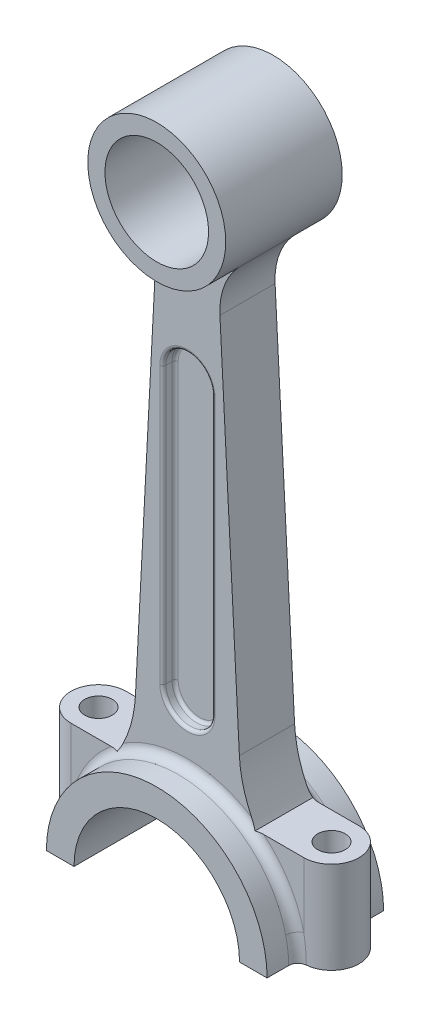
SolidWorks part; units mm, degrees
ref_plane "Front Plane" through (0, 0, 0) normal (0, 0, 1) x (1, 0, 0)
ref_plane "Top Plane" through (0, 0, 0) normal (0, 1, 0) x (1, 0, 0)
ref_plane "Right Plane" through (0, 0, 0) normal (1, 0, 0) x (0, 0, -1)
sketch "Sketch1" plane through (0, 0, 0) normal (0, 0, 1) x (1, 0, 0)
  line L0 (0, 0) -> (0, -201.2) construction
  line L1 (-10, -20.1556) -> (-17.8497, -169.9368)
  line L2 (10, -20.1556) -> (17.8497, -169.9368)
  line L3 (-36, -201.2) -> (-27, -201.2)
  line L4 (27, -201.2) -> (36, -201.2)
  circle A0 centre (0, 0) radius 16.9
  circle A1 centre (0, 0) radius 22.5
  arc A2 (27, -201.2) -> (-27, -201.2) centre (0, -201.2) ccw
  arc A3 (36, -201.2) -> (-36, -201.2) centre (0, -201.2) ccw
  dimension "D1" = 45
  dimension "D2" = 33.8
  dimension "D3" = 72
  dimension "D4" = 54
  dimension "D5" = 201.2
  dimension "D6" = 20
  dimension "D7" = 6
extrude "Boss-Extrude1" add sketch "Sketch1" along normal mid plane 38 contours A0 A1 | A3 A2 | L3 A2 L4 A3 region at (-11.5231, 18.5805, 0) region at (0, -166.005, 0)
extrude "Boss-Extrude2" add sketch "Sketch1<3>" along normal mid plane 18 contours L0 A1 L1 A3 | A1 L0 A3 L2 region at (7.1843, -100.8455, 0) region at (-7.1843, -100.8455, 0)
sketch "Sketch1<3>" plane through (0, 0, 0) normal (0, 0, 1) x (1, 0, 0) same geometry as "Sketch1"
sketch "Sketch2" plane through (0, 0, 9) normal (0, 0, 1) x (1, 0, 0)
  line L0 (0, 0) -> (0, -201.2) construction
  line L1 (0, -145.6) -> (0, -55.6) construction
  line L2 (-8, -145.6) -> (-8, -55.6)
  line L3 (8, -145.6) -> (8, -55.6)
  arc A0 (-8, -145.6) -> (8, -145.6) centre (0, -145.6) ccw
  arc A1 (8, -55.6) -> (-8, -55.6) centre (0, -55.6) ccw
  point P6 (0, -100.6)
  dimension "D2" = 8
  dimension "D1" = 90
extrude "Cut-Extrude1" cut sketch "Sketch2" against normal blind 4
mirror "Mirror1" about plane through (0, 0, 0) normal (0, 0, 1) of "Cut-Extrude1"
fillet "Fillet1" radius 1 16 edges at (-8, -100.6, -5) (0, -47.6, -5) (8, -100.6, -5) (-8, -100.6, -9) (0, -47.6, -9) (8, -100.6, -9) (0, -47.6, 9) (8, -100.6, 9) (0, -153.6, 9) (0, -153.6, -5) (0, -153.6, -9) (-8, -100.6, 9) (-8, -100.6, 5) (0, -47.6, 5) (8, -100.6, 5) (0, -153.6, 5)
ref_plane "Plane1" through (0, -171.2, 0) normal (0, -1, 0) x (-1, 0, 0)
fillet "Fillet3" radius 40 2 edges at (-17.8497, -169.9368, 0) (17.8497, -169.9368, 0)
sketch "Sketch3" plane through (0, -171.2, 0) normal (0, -1, 0) x (-1, 0, 0)
  line L0 (38, 0) -> (-38, 0) construction
  line L1 (38, -9) -> (-38, -9)
  line L2 (38, 9) -> (-38, 9)
  arc A0 (38, -9) -> (38, 9) centre (38, 0) ccw
  arc A1 (-38, 9) -> (-38, -9) centre (-38, 0) ccw
  point P2 (0, 0)
  dimension "D2" = 9
  dimension "D1" = 76
extrude "Boss-Extrude3" add sketch "Sketch3" along normal up to surface (30 mm away) up to face at (31.5, -201.2, 0)
sketch "Sketch4" plane through (0, 0, -9) normal (0, 0, -1) x (-1, 0, 0)
  line L1 (-27, -201.2) -> (27, -201.2)
  line L2 (-27, -201.2) -> (27, -201.2)
  arc A1 (27, -201.2) -> (-27, -201.2) centre (0, -201.2) ccw
  arc A2 (27, -201.2) -> (-27, -201.2) centre (0, -201.2) ccw
  dimension "D1" = 0
extrude "Cut-Extrude2" cut sketch "Sketch4" against normal through all
sketch "Sketch5" plane through (0, -171.2, 0) normal (0, 1, 0) x (1, 0, 0)
  circle A0 centre (-38, 0) radius 4.5
  circle A1 centre (38, 0) radius 4.5
  dimension "D1" = 9
  dimension "D2" = 9
extrude "Cut-Extrude3" cut sketch "Sketch5" against normal through all
fillet "Fillet2" radius 22.5 2 edges at (-10, -20.1556, 0) (10, -20.1556, 0)
fillet "Fillet4" radius 3 2 edges at (0, -165.2, -9) (0, -165.2, 9)
